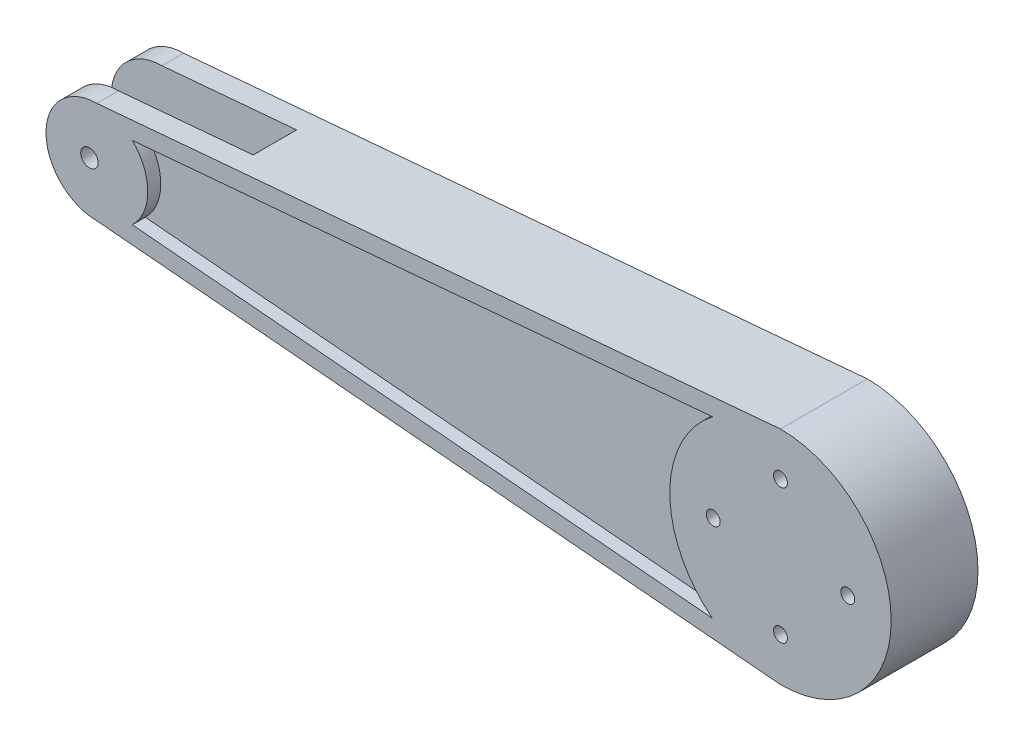
SolidWorks part; units mm, degrees
ref_plane "Front Plane" through (0, 0, 0) normal (1, 0, 0) x (0, 1, 0)
ref_plane "Top Plane" through (0, 0, 0) normal (0, 0, 1) x (0, 1, 0)
ref_plane "Right Plane" through (0, 0, 0) normal (0, 1, 0) x (-1, 0, 0)
sketch "Sketch1" plane through (0, 0, 0) normal (0, 0, 1) x (-1, 0, 0)
  line L17 (194.7068, 0) -> (186.7068, 0)
  line L21 (161.7175, 0) -> (182.7068, 0)
  line L24 (0, 0) -> (8.4, 0)
  line L25 (25.5, 25.5) -> (182.985, 11.7218)
  line L26 (11.6, 0) -> (39.4, 0)
  line L27 (42.6, 0) -> (161.7175, 0)
  arc A9 (182.985, 11.7218) -> (194.7068, 0) centre (182.985, 0) cw
  circle A13 centre (182.985, 0) radius 11.7218 construction
  arc A14 (25.5, 25.5) -> (0, 0) centre (25.5, 0) ccw
  circle A15 centre (25.5, 0) radius 15.5 construction
  arc A16 (11.6, 0) -> (8.4, 0) centre (10, 0) ccw
  circle A17 centre (25.5, 15.5) radius 1.6
  arc A18 (42.6, 0) -> (39.4, 0) centre (41, 0) ccw
  circle A19 centre (25.5, -15.5) radius 1.6 construction
  arc A20 (186.7068, 0) -> (182.7068, 0) centre (184.7068, 0) ccw
  point P2 (182.985, 10)
  point P9 (182.7068, 11.7218)
  point P13 (199.4473, 0)
  point P21 (182.985, 13.5533)
  point P27 (184.985, 0)
  point P28 (0, 0)
  point P29 (0, 0)
  point P30 (180.985, 0)
  point P31 (184.985, 0)
  point P32 (192.985, 0)
  point P33 (0, 0)
  point P34 (196.6256, 0)
  point P35 (182.7068, 11.7218)
  point P36 (194.7068, 0)
  point P37 (182.7068, 11.7218)
  point P38 (25.5, 25.5)
  point P39 (42.6, 0)
  point P40 (25.5, 15.5)
  point P41 (25.5, 25.5)
  point P42 (194.7068, 0)
  point P43 (0, 0)
  point P44 (182.985, 0)
  point P45 (182.7068, 0)
  point P46 (182.7068, 11.7218)
  point P47 (167.3657, 11.7218)
  dimension "D4" = 31
  dimension "D12" = 3.2
  dimension "D5" = 4
  dimension "D7" = 10
  dimension "D8" = 22.9893
  dimension "D3" = 157.485
  dimension "D10" = 10
  dimension "D11" = 3.2
  dimension "D13" = 4
  dimension "D6" = 5
  dimension "D2" = 4
extrude "Boss-Extrude1" add sketch "Sketch1" along normal blind 20
mirror "Mirror1" about plane through (0, 0, 20) normal (0, -1, 0) of "Boss-Extrude1"
ref_plane "Plane1" through (0, 0, 10) normal (0, 0, 1) x (1, 0, 0)
sketch "Sketch2" plane through (0, 0, 10) normal (0, 0, 1) x (1, 0, 0)
  line L0 (-174.6964, -8.2886) -> (-151.9727, 14.4351) construction
  line L1 (-182.985, 11.7218) -> (-25.5, 25.5) construction
  line L2 (-182.985, -11.7218) -> (-25.5, -25.5) construction
  line L3 (-151.9727, 14.4351) -> (-182.985, 11.7218)
  line L4 (-182.985, -11.7218) -> (-151.9727, -14.4351)
  line L10 (-151.9727, 14.4351) -> (-151.9727, -14.4351)
  arc A0 (-182.985, 11.7218) -> (-182.985, -11.7218) centre (-182.985, 0) ccw
  arc A4 (-182.985, 11.7218) -> (-182.985, -11.7218) centre (-182.985, 0) cw construction
  arc A8 (-182.985, 11.7218) -> (-182.985, -11.7218) centre (-182.985, 0) ccw construction
  point P0 (0, 0)
  point P3 (-162.9227, -3.7802)
  point P5 (0, 0)
  point P10 (-151.8872, -13.0607)
  dimension "D1" = 45
extrude "Cut-Extrude1" cut sketch "Sketch2" against normal blind 5 and the other way blind 5 contours L3 A0 L4 L10 region at (-171.3595, 0, 10)
sketch "Sketch3" plane through (0, 0, 20) normal (0, 0, 1) x (1, 0, 0)
  line L0 (-174.83, 8.42) -> (-41.1749, 20.1133)
  line L1 (-174.83, -8.42) -> (-41.1749, -20.1133)
  line L2 (-182.985, 11.7218) -> (-25.5, 25.5) construction
  line L3 (-182.985, -11.7218) -> (-25.5, -25.5) construction
  arc A0 (-174.83, -8.42) -> (-174.83, 8.42) centre (-182.985, 0) ccw
  arc A1 (-41.1749, 20.1133) -> (-41.1749, -20.1133) centre (-25.5, 0) ccw
  arc A2 (-25.5, -25.5) -> (-25.5, 25.5) centre (-25.5, 0) ccw construction
  arc A3 (-182.985, 11.7218) -> (-182.985, -11.7218) centre (-182.985, 0) ccw construction
  dimension "D1" = 4
  dimension "D2" = 4
extrude "Cut-Extrude2" cut sketch "Sketch3" against normal blind 3 contours L0 A1 L1 A0
mirror "Mirror2" about plane through (0, 0, 10) normal (0, 0, 1) of "Cut-Extrude2"
equation "\"ThighLength\"= 200"
equation "\"BearingBore\"=4"
equation "\"MinShinWidth\"= 20"
equation "\"HipBore\"=27"
equation "\"ShinThickness\"=10"
equation "\"ThighThickness\"=20"
equation "\"D1@Boss-Extrude1\"=\"ThighThickness\""
equation "\"D2@Cut-Extrude1\"=\"ShinThickness\"/2"
equation "\"D1@Cut-Extrude1\"=\"ShinThickness\"/2"
equation "\"MaxBending\"=135"
equation "\"D1@Sketch2\"=180-\"MaxBending\""
equation "\"MaxStretchingAngle\"= 140"
equation "\"KneeLength\" =20"
equation "\"ThighJointDistance\"=157.485"
equation "\"D3@Sketch1\"=\"ThighJointDistance\""
